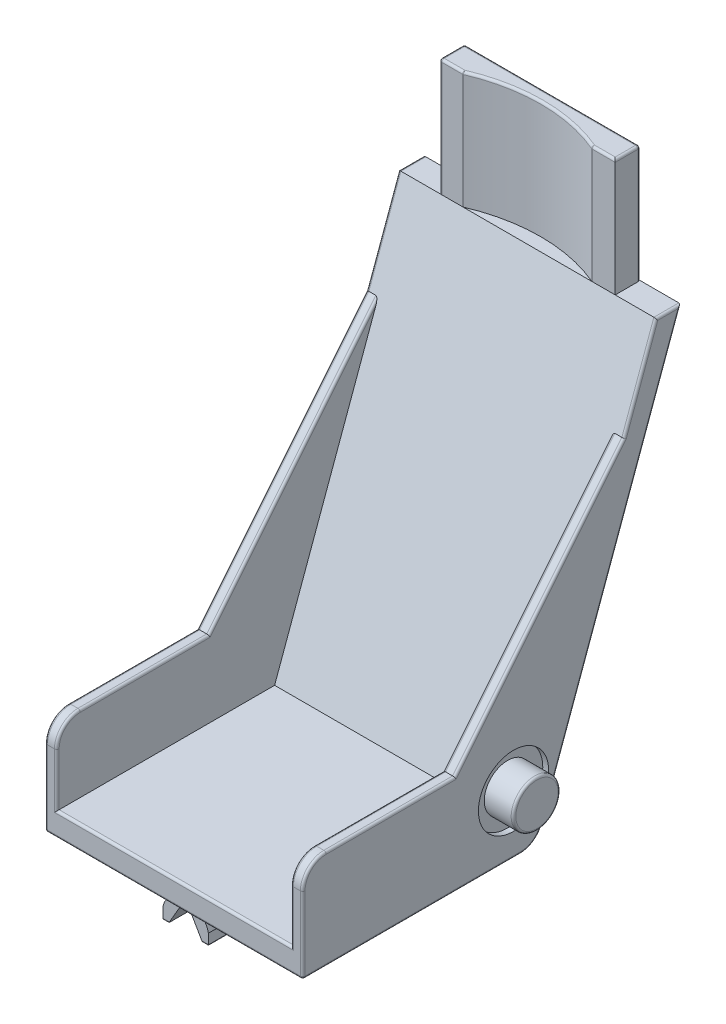
SolidWorks part; units mm, degrees
ref_plane "前视基准面" through (0, 0, 0) normal (0, 0, 1) x (1, 0, 0)
ref_plane "上视基准面" through (0, 0, 0) normal (0, 1, 0) x (1, 0, 0)
ref_plane "右视基准面" through (0, 0, 0) normal (1, 0, 0) x (0, 0, -1)
sketch "草图1" plane through (0, 0, 0) normal (1, 0, 0) x (0, 0, -1)
  line L0 (0, 0) -> (20, 0)
  line L1 (20, 0) -> (32.3127, 33.8289)
  line L2 (0, 2) -> (0, 0)
  line L3 (0, 2) -> (18.5996, 2)
  line L4 (18.5996, 2) -> (30.1844, 33.8289)
  line L5 (32.3127, 33.8289) -> (30.1844, 33.8289)
  line L6 (32.3127, 33.8289) -> (32.3127, 43.8289) construction
  line L7 (30.3127, 34.1816) -> (30.3127, 43.8289) construction
  line L9 (18.5996, 2) -> (30.3127, 34.1816) construction
  dimension "D1" = 20
  dimension "D2" = 36
  dimension "D3" = 110
  dimension "D5" = 2
extrude "凸台-拉伸1" add sketch "草图1" along normal blind 11 and the other way blind 11
sketch "草图2" plane through (11, 0, 0) normal (1, 0, 0) x (0, 0, -1)
  line L0 (0, 0) -> (20, 0)
  line L1 (20, 0) -> (29.5766, 26.3114)
  line L2 (20, 0) -> (32.3127, 33.8289) construction
  line L3 (29.5766, 26.3114) -> (27.4482, 26.3114)
  line L4 (30.1844, 33.8289) -> (18.5996, 2) construction
  line L5 (27.4482, 26.3114) -> (13, 8.5)
  line L6 (13, 8.5) -> (0, 8.5)
  line L7 (0, 8.5) -> (0, 0)
  dimension "D1" = 13
  dimension "D2" = 8.5
  dimension "D3" = 28
extrude "凸台-拉伸2" add sketch "草图2" against normal blind 1
mirror "镜向1" about plane through (0, 0, 0) normal (1, 0, 0) of "凸台-拉伸2"
sketch "草图3" plane through (0, 0, 0) normal (1, 0, 0) x (0, 0, -1)
  line L0 (32.3127, 33.8289) -> (32.3127, 43.8289)
  line L1 (30.1844, 33.8289) -> (30.1844, 43.8289)
  line L2 (30.1844, 43.8289) -> (32.3127, 43.8289)
  line L3 (30.1844, 33.8289) -> (32.3127, 33.8289)
  dimension "D1" = 10
extrude "凸台-拉伸3" add sketch "草图3" along normal blind 7.5 and the other way blind 7.5
sketch "草图4" plane through (0, 43.8289, 0) normal (0, 1, 0) x (1, 0, 0)
  line L0 (-7.5, 30.1844) -> (-5.5, 30.1844) construction
  line L1 (-7.5, 30.1844) -> (7.5, 30.1844) construction
  line L2 (7.5, 30.1844) -> (5.5, 30.1844) construction
  line L3 (-5.5, 30.1844) -> (5.5, 30.1844)
  line L4 (0, 32.3127) -> (0, 31.3127) construction
  line L5 (-7.5, 32.3127) -> (7.5, 32.3127) construction
  arc A0 (5.5, 30.1844) -> (-5.5, 30.1844) centre (0, 17.3441) ccw
  dimension "D1" = 2
  dimension "D2" = 2
  dimension "D3" = 1
extrude "切除-拉伸1" cut sketch "草图4" against normal blind 10
sketch "草图5" plane through (11, 0, 0) normal (1, 0, 0) x (0, 0, -1)
  line L0 (0, 8.5) -> (0, 0) construction
  line L3 (0, 0) -> (20, 0) construction
  circle A0 centre (18, 5) radius 3
  dimension "D3" = 6
  dimension "D1" = 18
  dimension "D2" = 5
extrude "切除-拉伸2" cut sketch "草图5" against normal blind 0.5
sketch "草图6" plane through (10.5, 0, 0) normal (1, 0, 0) x (0, 0, -1)
  circle A0 centre (18, 5) radius 2
  dimension "D1" = 4
extrude "凸台-拉伸4" add sketch "草图6" along normal blind 2.5
mirror "镜向2" about plane through (0, 0, 0) normal (1, 0, 0) of "凸台-拉伸4", "切除-拉伸2"
sketch "草图7" plane through (0, 0, 0) normal (0, 0, 1) x (1, 0, 0)
  line L0 (0, 0) -> (0, -2) construction
  line L1 (0, -2) -> (0, -2.5) construction
  line L2 (0, 0) -> (-1.5, 0)
  line L3 (-11, 0) -> (11, 0) construction
  line L4 (-1.5, 0) -> (-1.5, -0.6771)
  line L5 (-1.4434, -2.5) -> (-1.95, -2.5)
  line L6 (-1.95, -2.5) -> (-1.95, -1.5556)
  line L7 (0, 0) -> (-1.4434, -2.5)
  arc A0 (-1.5, -0.6771) -> (-1.95, -1.5556) centre (0, -2) ccw
  dimension "D1" = 2
  dimension "D2" = 0.5
  dimension "D3" = 1.5
  dimension "D4" = 1.95
  dimension "D5" = 30
extrude "凸台-拉伸5" add sketch "草图7" against normal blind 14 from offset 1 offset against normal yes
mirror "镜向3" about plane through (0, 0, 0) normal (1, 0, 0) of "凸台-拉伸5"
fillet "圆角1" radius 2 3 edges at (0, 0, -20) (-10.5, 8.5, 0) (10.5, 8.5, 0)
fillet "圆角3" radius 0.2 14 edges at (10, 8.5, -7.5) (10, 7.9142, -0.5858) (11, 8.5, -7.5) (11, 7.9142, -0.5858) (-11, 8.5, -7.5) (-11, 7.9142, -0.5858) (-10, 8.5, -7.5) (-10, 7.9142, -0.5858) (0, 2, 0) (10, 4.25, 0) (11, 3.25, 0) (0, 0, 0) (-11, 3.25, 0) (-10, 4.25, 0)
fillet "圆角5" radius 0.2 4 edges at (11, 17.3057, -20.143) (10, 17.3057, -20.143) (-10, 17.3057, -20.143) (-11, 17.3057, -20.143)
fillet "圆角7" radius 0.2 12 edges at (-10.9414, 0.0586, -0.0586) (-11, 0, -9.3998) (-11, 0.3617, -19.7467) (10.9414, 0.0586, -0.0586) (11, 0, -9.3998) (11, 0.3617, -19.7467) (-11, 33.8289, -31.2485) (11, 33.8289, -31.2485) (-11, 17.5724, -26.3958) (11, 17.5724, -26.3958) (11, 29.7822, -28.7115) (-11, 29.7822, -28.7115)
fillet "圆角10" radius 0.2 11 edges at (-6.5, 43.8289, -30.1844) (-7.5, 43.8289, -31.2485) (0, 43.8289, -32.3127) (7.5, 43.8289, -31.2485) (6.5, 43.8289, -30.1844) (0, 43.8289, -31.3127) (5.5, 38.8289, -30.1844) (-5.5, 38.8289, -30.1844)
fillet "圆角11" radius 0.1 8 edges at (1.95, -2.5, -8) (1.6967, -2.5, -15) (1.4434, -2.5, -8) (1.6967, -2.5, -1) (-1.4434, -2.5, -8) (-1.6967, -2.5, -15) (-1.95, -2.5, -8) (-1.6967, -2.5, -1)
fillet "圆角12" radius 0.2 2 edges at (-13, 5, -20) (13, 5, -20)
